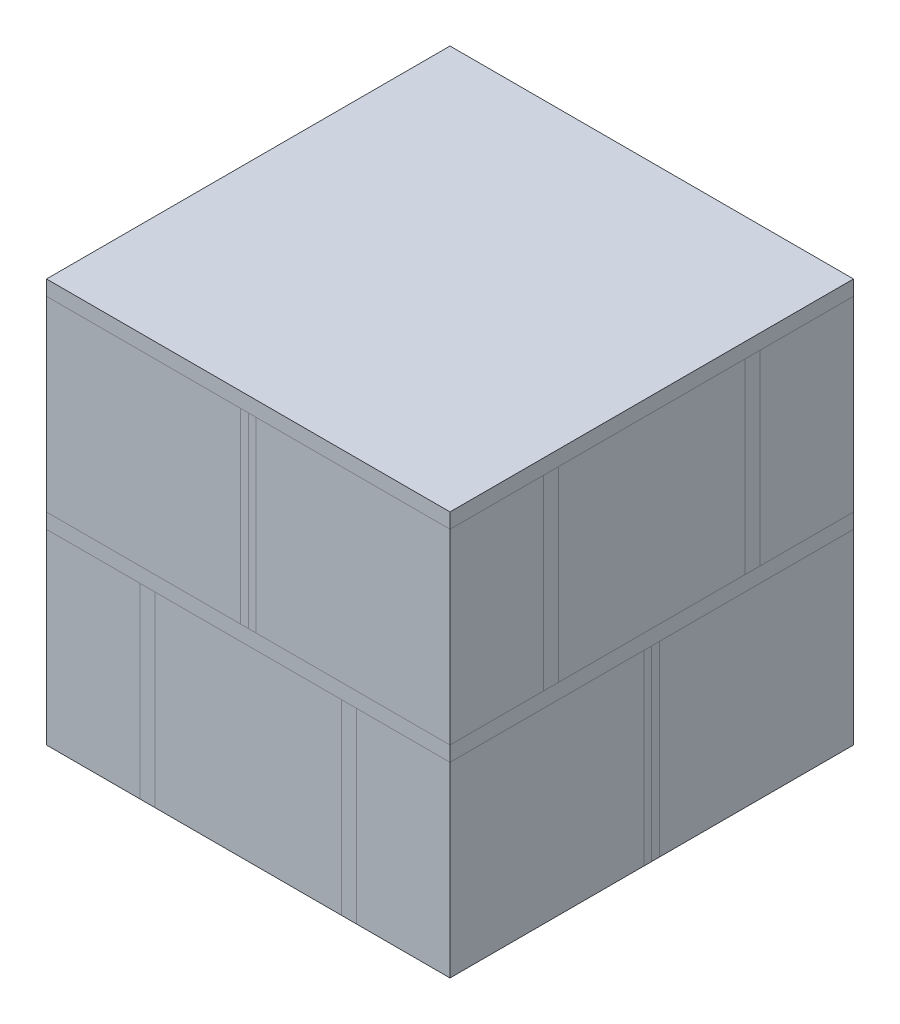
SolidWorks part; units mm, degrees
other "Камера1"
ref_plane "Спереди" through (0, 0, 0) normal (0, 0, 1) x (1, 0, 0)
ref_plane "Сверху" through (0, 0, 0) normal (0, 1, 0) x (1, 0, 0)
ref_plane "Справа" through (0, 0, 0) normal (1, 0, 0) x (0, 0, -1)
sketch "Эскиз2" plane through (0, 0, 0) normal (0, 1, 0) x (1, 0, 0)
  line L1 (13.435, -13.435) -> (-13.435, -13.435)
  line L2 (13.435, -13.435) -> (13.435, 13.435)
  line L3 (13.435, 13.435) -> (-13.435, 13.435)
  line L4 (-13.435, -13.435) -> (-13.435, 13.435)
  line L5 (13.435, -13.435) -> (-13.435, 13.435) construction
  line L6 (13.435, 13.435) -> (-13.435, -13.435) construction
  point P0 (0, 0)
  dimension "D1" = 38
  dimension "D2" = 26.8701
ref_plane "Плоскость1" through (0, 26.8701, 0) normal (0, 1, 0) x (1, 0, 0)
ref_plane "Плоскость2" through (0, 0, -13.435) normal (0, 0, 1) x (1, 0, 0)
ref_plane "Плоскость3" through (-13.435, 0, 0) normal (1, 0, 0) x (0, 0, -1)
extrude "Бобышка-Вытянуть1" [suppressed] add sketch "Эскиз2" along normal blind 26.87
pattern_linear "Линейный массив1" [suppressed] count 2 spacing 26.87 count 2 spacing 26.87 of bodies 108
sketch "Эскиз3" plane through (0, 0, 0) normal (0, 1, 0) x (1, 0, 0)
  line L0 (6.22, -0.5) -> (6.22, -13.435)
  line L5 (13.435, 13.435) -> (-13.435, 13.435)
  line L6 (13.435, 13.435) -> (13.435, -13.435)
  line L11 (13.435, -13.435) -> (-13.435, -13.435)
  line L12 (-13.435, 13.435) -> (-13.435, -13.435)
  line L21 (13.435, 13.435) -> (-13.435, -13.435) construction
  line L22 (13.435, -13.435) -> (-13.435, 13.435) construction
  line L23 (-13.435, 0) -> (13.435, 0)
  line L24 (-6.72, 0) -> (-6.72, -13.435)
  line L25 (-6.72, -13.435) -> (6.72, -13.435)
  line L26 (6.72, 0) -> (6.72, -13.435)
  line L27 (-6.22, -0.5) -> (6.22, -0.5)
  line L28 (-6.22, -0.5) -> (-6.22, -13.435)
  line L29 (-6.72, 0) -> (6.72, 0) construction
  line L30 (0, -13.435) -> (0, 0) construction
  line L31 (13.435, -0.5) -> (7.22, -0.5)
  line L32 (-13.435, -13.435) -> (-7.22, -13.435)
  line L33 (-13.435, -13.435) -> (-13.435, -0.5)
  line L34 (-13.435, -0.5) -> (-7.22, -0.5)
  line L35 (-7.22, -13.435) -> (-7.22, -0.5)
  line L36 (7.22, -13.435) -> (7.22, -0.5)
  point P0 (0, 0)
  dimension "D1" = 26.87
  dimension "D2" = 13.44
  dimension "D3" = 0.5
  dimension "D4" = 0.5
extrude "Бобышка-Вытянуть2" add sketch "Эскиз3" along normal blind 12.44 contours L11 L35 L34 L12 | L27 L28 L11 L0 | L36 L11 L6 L31 region at (0, 0, 6.9675) region at (10.3275, 0, 6.9675) region at (-10.3275, 0, 6.9675)
extrude "Бобышка-Вытянуть3" add sketch "Эскиз3<4>" along normal up to surface (12.44 mm away) separate body contours L28 L27 L0 L11 L26 L23 L24 L25 | L11 L36 L31 L6 L23 L26 | L35 L11 L24 L23 L12 L34 region at (0, 0, 0.31) region at (6.8702, 0, 6.7175) region at (-6.97, 0, 13.2848) up to face at (0, 12.44, 6.9675)
sketch "Эскиз3<4>" plane through (0, 0, 0) normal (0, 1, 0) x (1, 0, 0) same geometry as "Эскиз3"
mirror "Зеркальное отражение1" about plane through (0, 0, 0) normal (0, 0, 1) of bodies 211 136 209 210
sketch "Эскиз4" plane through (0, 12.44, 0) normal (0, 1, 0) x (1, 0, 0)
  line L1 (13.435, -13.435) -> (-13.435, -13.435)
  line L2 (13.435, -13.435) -> (13.435, 13.435)
  line L3 (13.435, 13.435) -> (-13.435, 13.435)
  line L4 (-13.435, -13.435) -> (-13.435, 13.435)
extrude "Бобышка-Вытянуть4" add sketch "Эскиз4" along normal blind 1 separate body
sketch "Эскиз6" plane through (0, 13.44, 0) normal (0, 1, 0) x (1, 0, 0)
  line L0 (0.5, 6.22) -> (13.435, 6.22)
  line L5 (-13.435, 13.435) -> (-13.435, -13.435)
  line L6 (-13.435, 13.435) -> (13.435, 13.435)
  line L11 (13.435, 13.435) -> (13.435, -13.435)
  line L12 (-13.435, -13.435) -> (13.435, -13.435)
  line L21 (-13.435, 13.435) -> (13.435, -13.435) construction
  line L22 (13.435, 13.435) -> (-13.435, -13.435) construction
  line L23 (0, -13.435) -> (0, 13.435)
  line L24 (0, -6.72) -> (13.435, -6.72)
  line L25 (13.435, -6.72) -> (13.435, 6.72)
  line L26 (0, 6.72) -> (13.435, 6.72)
  line L27 (0.5, -6.22) -> (0.5, 6.22)
  line L28 (0.5, -6.22) -> (13.435, -6.22)
  line L30 (13.435, 0) -> (0, 0) construction
  line L31 (0.5, 13.435) -> (0.5, 7.22)
  line L32 (13.435, -13.435) -> (13.435, -7.22)
  line L33 (13.435, -13.435) -> (0.5, -13.435)
  line L34 (0.5, -13.435) -> (0.5, -7.22)
  line L35 (13.435, -7.22) -> (0.5, -7.22)
  line L36 (13.435, 7.22) -> (0.5, 7.22)
  point P0 (0, 0)
  point P6 (0, 0)
  point P7 (0, 0)
  point P8 (0, 0)
  point P9 (0, 0)
  point P10 (0, 0)
  point P11 (0, 0)
  point P12 (0, 0)
  point P13 (0, 0)
  point P19 (0, 0)
  point P25 (0, 0)
  point P34 (12.2449, -4.899)
  point P35 (11.1424, 4.9074)
  point P36 (0, 0)
  line M43 (13.435, -13.435) -> (13.435, 13.435)
  line M44 (13.435, 13.435) -> (-13.435, 13.435)
  dimension "D1" = 26.87
  dimension "D2" = 13.44
  dimension "D3" = 0.5
  dimension "D4" = 0.5
  dimension "D5" = 0.5
extrude "Бобышка-Вытянуть5" add sketch "Эскиз6" along normal blind 12.44 separate body contours L35 L34 L12 M43 | L27 L28 L0 M43 | L36 L31 M43 M44 region at (6.9675, 13.44, 0) region at (6.9675, 13.44, -10.3275) region at (6.9675, 13.44, 10.3275)
extrude "Бобышка-Вытянуть6" add sketch "Эскиз6<6>" along normal up to surface (12.44 mm away) separate body contours L35 L11 L24 L23 L12 L34 | L28 L27 L0 L26 L23 L24 L11 M43 | L11 L36 L31 L6 L23 L26 region at (0.31, 13.44, 0) region at (6.7175, 13.44, -6.8702) region at (13.2848, 13.44, 6.97) up to face at (6.9675, 25.88, 0)
sketch "Эскиз6<6>" plane through (0, 13.44, 0) normal (0, 1, 0) x (1, 0, 0) same geometry as "Эскиз6"
mirror "Зеркальное отражение2" about plane through (0, 0, 0) normal (1, 0, 0) of bodies 218 219 217 220
pattern_linear "Линейный массив2" count 2 spacing 13.44 along (0, 1, 0) of "Бобышка-Вытянуть4"
equation "\"x\"= \"D2@Эскиз2\""
equation "\"half\"= \"D2@Эскиз2\" / 2"
